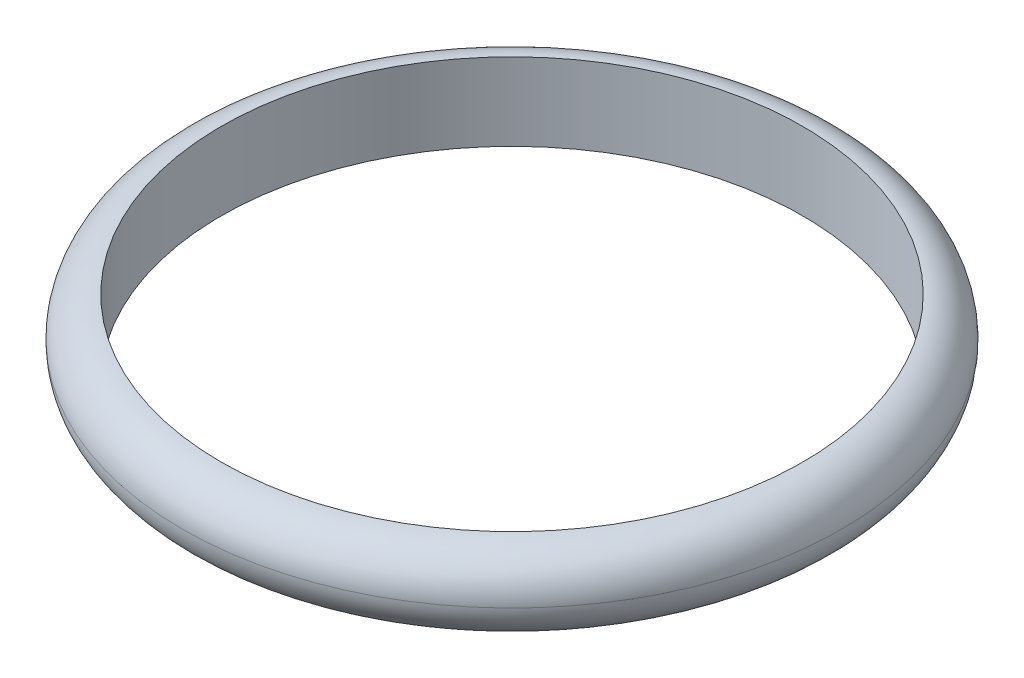
SolidWorks part; units mm, degrees
ref_plane "Face" through (0, 0, 0) normal (0, 0, 1) x (1, 0, 0)
ref_plane "Dessus" through (0, 0, 0) normal (0, 1, 0) x (1, 0, 0)
ref_plane "Droite" through (0, 0, 0) normal (1, 0, 0) x (0, 0, -1)
sketch "Esquisse1" plane through (0, 0, 0) normal (0, 1, 0) x (1, 0, 0)
  circle A0 centre (0, 0) radius 17
  circle A1 centre (0, 0) radius 15
  dimension "D1" = 34
  dimension "D2" = 30
extrude "Extrusion1" add sketch "Esquisse1" along normal blind 4
fillet "Congé1" radius 2 2 edges at (0, 0, 17) (0, 4, 17)
